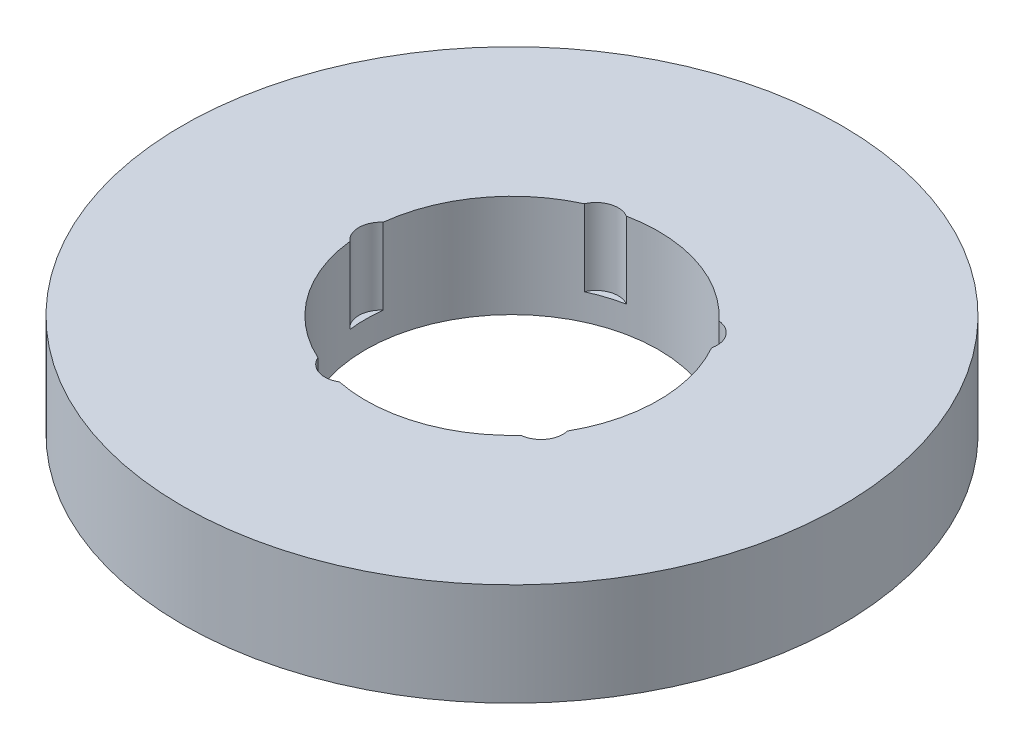
SolidWorks part; units mm, degrees
ref_plane "Front Plane" through (0, 0, 0) normal (0, 0, 1) x (1, 0, 0)
ref_plane "Top Plane" through (0, 0, 0) normal (0, 1, 0) x (1, 0, 0)
ref_plane "Right Plane" through (0, 0, 0) normal (1, 0, 0) x (0, 0, -1)
sketch "Sketch1" plane through (0, 0, 0) normal (0, 1, 0) x (1, 0, 0)
  circle A0 centre (0, 0) radius 45
  dimension "FLANGE_OD" = 90
extrude "Boss-Extrude1" add sketch "Sketch1" along normal blind 14
sketch "Sketch2" plane through (0, 0, 0) normal (0, 1, 0) x (1, 0, 0)
  circle A0 centre (0, 0) radius 20
  dimension "BORE_D" = 40
extrude "Cut-Extrude1" cut sketch "Sketch2" along normal through all
sketch "Sketch3" plane through (0, 14, 0) normal (0, 1, 0) x (1, 0, 0)
  circle A0 centre (0, 0) radius 17.8834 construction
  circle A1 centre (-17.8834, 0) radius 3.0228
  dimension "BOLT_D" = 6.0456
  dimension "BOLT_PCD" = 35.7668
extrude "Cut-Extrude2" cut sketch "Sketch3" against normal blind 10.4057
pattern_circular "CirPattern1" count 5 over 360 about axis through (0, 0, 0) along (0, 1, 0) of "Cut-Extrude2"
